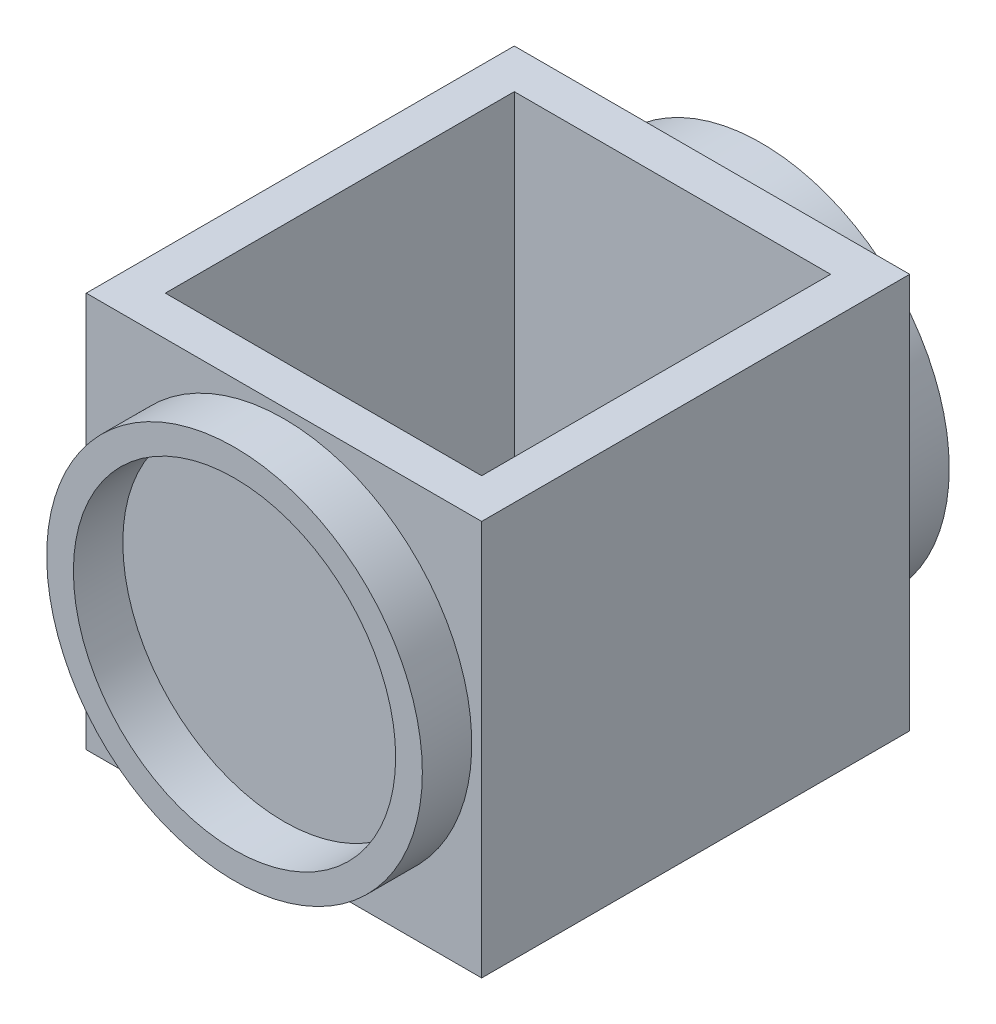
SolidWorks part; units mm, degrees
ref_plane "Front Plane" through (0, 0, 0) normal (0, 0, 1) x (1, 0, 0)
ref_plane "Top Plane" through (0, 0, 0) normal (0, 1, 0) x (1, 0, 0)
ref_plane "Right Plane" through (0, 0, 0) normal (1, 0, 0) x (0, 0, -1)
sketch "Sketch1" plane through (0, 0, 0) normal (0, 0, 1) x (1, 0, 0)
  line L1 (-25.4, 25.4) -> (25.4, 25.4)
  line L2 (-25.4, 25.4) -> (-25.4, -25.4)
  line L3 (-25.4, -25.4) -> (25.4, -25.4)
  line L4 (25.4, 25.4) -> (25.4, -25.4)
  point P4 (0, 25.4)
  point P6 (25.4, 0)
  dimension "D1" = 50.8
  dimension "D2" = 50.8
extrude "Boss-Extrude1" add sketch "Sketch1" along normal up to surface (54.991 mm away) contours L4 L3 L2 L1
sketch "Sketch2" plane through (0, 25.4, 0) normal (0, 1, 0) x (1, 0, 0)
  line L8 (-20.32, -49.911) -> (20.32, -49.911)
  line L9 (20.32, -49.911) -> (20.32, -5.08)
  line L10 (20.32, -5.08) -> (-20.32, -5.08)
  line L11 (-20.32, -5.08) -> (-20.32, -49.911)
  line L12 (-20.32, -49.911) -> (20.32, -49.911)
  line L13 (20.32, -49.911) -> (20.32, -5.08)
  line L14 (20.32, -5.08) -> (-20.32, -5.08)
  line L15 (-20.32, -5.08) -> (-20.32, -49.911)
  dimension "D1" = 5.08
extrude "Cut-Extrude1" cut sketch "Sketch2" against normal through all
sketch "Sketch3" plane through (0, 0, 54.991) normal (0, 0, 1) x (1, 0, 0)
  circle A0 centre (0, 0) radius 20.701
  circle A1 centre (0, 0) radius 24.13
  dimension "D1" = 41.402
  dimension "D2" = 48.26
extrude "Boss-Extrude2" add sketch "Sketch3" along normal blind 6.35
ref_plane "Plane1" through (0, 0, 27.4955) normal (0, 0, 1) x (1, 0, 0)
mirror "Mirror1" about plane through (0, 0, 27.4955) normal (0, 0, 1) of "Boss-Extrude2"
